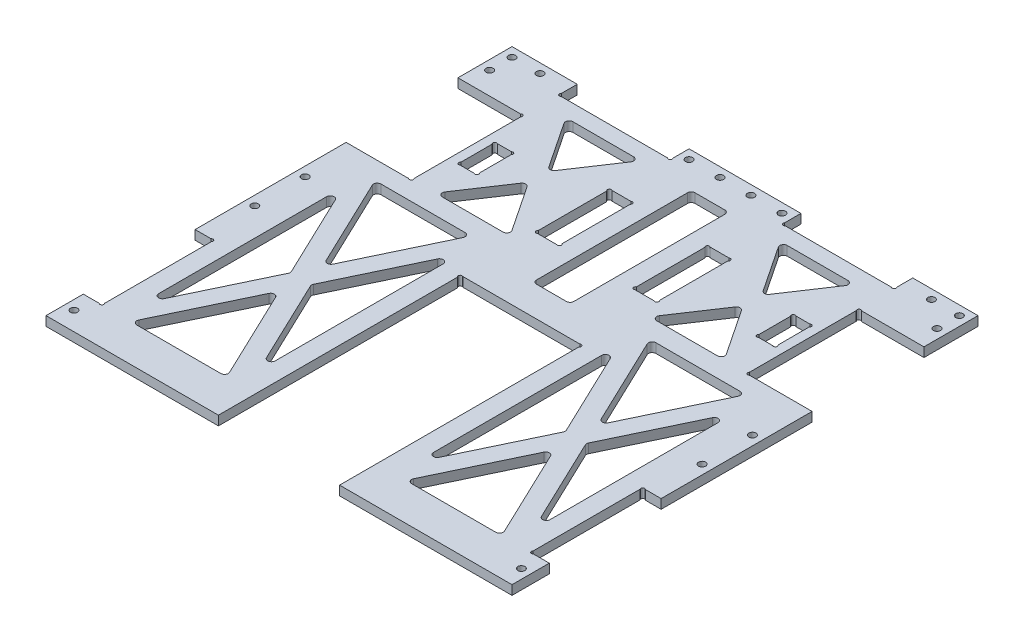
SolidWorks part; units mm, degrees
material "7050-T73510"
ref_plane "Front Plane" through (0, 0, 0) normal (0, 0, 1) x (1, 0, 0)
ref_plane "Top Plane" through (0, 0, 0) normal (0, 1, 0) x (1, 0, 0)
ref_plane "Right Plane" through (0, 0, 0) normal (1, 0, 0) x (0, 0, -1)
sketch "Sketch1" plane through (0, 0, 0) normal (0, 1, 0) x (1, 0, 0)
  line L0 (0, -55) -> (0, 55) construction
  line L1 (-158.75, -76.2) -> (158.75, -76.2)
  line L2 (-158.75, -76.2) -> (-158.75, 76.2)
  line L3 (-158.75, 76.2) -> (158.75, 76.2)
  line L4 (158.75, -76.2) -> (158.75, 76.2)
  line L5 (-158.75, -76.2) -> (158.75, 76.2) construction
  line L6 (-158.75, 76.2) -> (158.75, -76.2) construction
  line L7 (-158.75, -76.2) -> (-25.4, -76.2)
  line L8 (-158.75, -76.2) -> (-158.75, -241.3)
  line L9 (-158.75, -241.3) -> (-25.4, -241.3)
  line L10 (-25.4, -76.2) -> (-25.4, -241.3)
  line L11 (25.4, -76.2) -> (25.4, -241.3)
  line L12 (158.75, -241.3) -> (25.4, -241.3)
  line L13 (158.75, -76.2) -> (158.75, -241.3)
  line L14 (158.75, -76.2) -> (25.4, -76.2)
  line L15 (-41.275, -76.2) -> (-41.275, -241.3)
  line L16 (41.275, -76.2) -> (41.275, -241.3)
  point P0 (0, 0)
  dimension "D1" = 317.5
  dimension "D2" = 152.4
  dimension "D3" = 317.5
  dimension "D4" = 50.8
  dimension "D5" = 15.875
extrude "Boss-Extrude1" add sketch "Sketch1" along normal blind 6.35 contours L15 L1 L8 L9 | L14 L16 L12 L13 | L1 L7 L14 L4 L3 L2 region at (0, 0, 0) region at (-100.0125, 0, 158.75) region at (100.0125, 0, 158.75)
sketch "Sketch2" plane through (0, 6.35, 0) normal (0, 1, 0) x (1, 0, 0)
  line L0 (158.75, -241.3) -> (158.75, 76.2) construction
  line L1 (158.75, 39.37) -> (114.3, 39.37)
  line L2 (158.75, 39.37) -> (158.75, -36.83)
  line L3 (158.75, -36.83) -> (114.3, -36.83)
  line L4 (114.3, 39.37) -> (114.3, -36.83)
  line L5 (-158.75, 76.2) -> (158.75, 76.2) construction
  line L6 (158.75, -139.7) -> (146.05, -139.7)
  line L7 (158.75, -139.7) -> (158.75, -215.9)
  line L8 (158.75, -215.9) -> (146.05, -215.9)
  line L9 (146.05, -139.7) -> (146.05, -215.9)
  line L10 (0, -3.4925) -> (0, 3.4925) construction
  line L11 (-158.75, -215.9) -> (-146.05, -215.9)
  line L12 (-146.05, -139.7) -> (-146.05, -215.9)
  line L13 (-158.75, -139.7) -> (-146.05, -139.7)
  line L14 (-158.75, -139.7) -> (-158.75, -215.9)
  line L15 (-158.75, -36.83) -> (-114.3, -36.83)
  line L16 (-114.3, 39.37) -> (-114.3, -36.83)
  line L17 (-158.75, 39.37) -> (-114.3, 39.37)
  line L18 (-158.75, 39.37) -> (-158.75, -36.83)
  line L19 (-114.3, 63.5) -> (-38.1, 63.5)
  line L20 (114.3, 76.2) -> (38.1, 76.2)
  line L21 (114.3, 76.2) -> (114.3, 63.5)
  line L22 (114.3, 63.5) -> (38.1, 63.5)
  line L23 (38.1, 76.2) -> (38.1, 63.5)
  line L24 (-38.1, 76.2) -> (-38.1, 63.5)
  line L25 (-114.3, 76.2) -> (-38.1, 76.2)
  line L26 (-114.3, 76.2) -> (-114.3, 63.5)
  dimension "D1" = 44.45
  dimension "D2" = 12.7
  dimension "D3" = 76.2
  dimension "D4" = 76.2
  dimension "D5" = 36.83
  dimension "D6" = 215.9
  dimension "D7" = 76.2
  dimension "D8" = 12.7
  dimension "D9" = 76.2
extrude "Cut-Extrude1" cut sketch "Sketch2" against normal through all
sketch "Sketch4" plane through (0, 6.35, 0) normal (0, 1, 0) x (1, 0, 0)
  line L0 (41.275, -76.2) -> (41.275, -241.3) construction
  line L1 (53.975, -215.9) -> (133.35, -215.9)
  line L2 (53.975, -215.9) -> (53.975, -49.53)
  line L3 (53.975, -49.53) -> (133.35, -49.53)
  line L4 (133.35, -215.9) -> (133.35, -49.53)
  line L5 (146.05, -139.7) -> (146.05, -215.9) construction
  line L6 (158.75, -241.3) -> (41.275, -241.3) construction
  line L7 (53.975, -215.9) -> (133.35, -49.53) construction
  line L8 (53.975, -49.53) -> (133.35, -215.9) construction
  line L9 (133.35, -201.1532) -> (61.0107, -49.53)
  line L10 (126.3143, -215.9) -> (53.975, -64.2768)
  line L11 (53.975, -201.1532) -> (126.3143, -49.53)
  line L12 (61.0107, -215.9) -> (133.35, -64.2768)
  line L13 (114.3, -36.83) -> (158.75, -36.83) construction
  line L14 (0, -3.4925) -> (0, 3.4925) construction
  line L15 (-53.975, -201.1532) -> (-126.3143, -49.53)
  line L16 (-126.3143, -215.9) -> (-53.975, -64.2768)
  line L17 (-133.35, -201.1532) -> (-61.0107, -49.53)
  line L18 (-61.0107, -215.9) -> (-133.35, -64.2768)
  line L19 (-53.975, -49.53) -> (-133.35, -49.53)
  line L20 (-133.35, -215.9) -> (-133.35, -49.53)
  line L21 (-53.975, -215.9) -> (-133.35, -215.9)
  line L22 (-53.975, -215.9) -> (-53.975, -49.53)
  point P18 (116.9135, -166.7022)
  dimension "D1" = 12.7
  dimension "D2" = 12.7
  dimension "D3" = 25.4
  dimension "D4" = 12.7
  dimension "D5" = 12.7
extrude "Cut-Extrude3" cut sketch "Sketch4" against normal through all contours L12 L9 L4 | L12 L1 L10 | L2 L11 L10 | L9 L11 L3 | L21 L18 L16 | L20 L17 L18 | L17 L19 L15 | L15 L22 L16 region at (93.6625, 6.35, 193.0873) region at (64.8589, 6.35, 132.715) region at (122.4661, 6.35, 132.715) region at (93.6625, 6.35, 72.3427) region at (-64.8589, 6.35, 132.715) region at (-93.6625, 6.35, 72.3427) region at (-93.6625, 6.35, 193.0873) region at (-122.4661, 6.35, 132.715)
sketch "Sketch3" plane through (0, 6.35, 0) normal (0, 1, 0) x (1, 0, 0)
  line L0 (-41.275, -76.2) -> (41.275, -76.2) construction
  line L1 (-41.275, -25.4) -> (-25.4, -25.4)
  line L2 (-41.275, -25.4) -> (-41.275, 25.4)
  line L3 (-41.275, 25.4) -> (-25.4, 25.4)
  line L4 (-25.4, -25.4) -> (-25.4, 25.4)
  line L5 (0, -3.4925) -> (0, 3.4925) construction
  line L6 (41.275, 25.4) -> (25.4, 25.4)
  line L7 (25.4, -25.4) -> (25.4, 25.4)
  line L8 (41.275, -25.4) -> (25.4, -25.4)
  line L9 (41.275, -25.4) -> (41.275, 25.4)
  line L10 (114.3, 39.37) -> (114.3, -36.83) construction
  line L11 (95.25, 13.97) -> (107.95, 13.97)
  line L12 (95.25, 13.97) -> (95.25, -11.43)
  line L13 (95.25, -11.43) -> (107.95, -11.43)
  line L14 (107.95, 13.97) -> (107.95, -11.43)
  line L15 (38.1, 63.5) -> (114.3, 63.5) construction
  line L16 (-95.25, -11.43) -> (-107.95, -11.43)
  line L17 (-107.95, 13.97) -> (-107.95, -11.43)
  line L18 (-95.25, 13.97) -> (-107.95, 13.97)
  line L19 (-95.25, 13.97) -> (-95.25, -11.43)
  dimension "D1" = 50.8
  dimension "D2" = 15.875
  dimension "D3" = 50.8
  dimension "D4" = 50.8
  dimension "D5" = 25.4
  dimension "D6" = 12.7
  dimension "D7" = 6.35
  dimension "D8" = 49.53
extrude "Cut-Extrude2" cut sketch "Sketch3" against normal through all
sketch "Sketch6" plane through (0, 6.35, 0) normal (0, 1, 0) x (1, 0, 0)
  line L0 (-25.4, -25.4) -> (-25.4, 25.4) construction
  line L1 (-19.05, 63.5) -> (19.05, 63.5)
  line L2 (-19.05, 63.5) -> (-19.05, -63.5)
  line L3 (-19.05, -63.5) -> (19.05, -63.5)
  line L4 (19.05, 63.5) -> (19.05, -63.5)
  line L5 (25.4, 25.4) -> (25.4, -25.4) construction
  line L6 (-38.1, 76.2) -> (38.1, 76.2) construction
  line L7 (-41.275, -76.2) -> (41.275, -76.2) construction
  line L8 (-19.05, -63.5) -> (19.05, 63.5) construction
  line L9 (19.05, -63.5) -> (-19.05, 63.5) construction
  line L10 (12.4204, -63.5) -> (-19.05, 41.4014)
  line L11 (-12.4204, 63.5) -> (19.05, -41.4014)
  line L12 (-19.05, -41.4014) -> (12.4204, 63.5)
  line L13 (19.05, 41.4014) -> (-12.4204, -63.5)
  dimension "D1" = 6.35
  dimension "D2" = 6.35
  dimension "D3" = 12.7
  dimension "D4" = 12.7
  dimension "D5" = 12.7
  dimension "D6" = 12.7
extrude "Cut-Extrude5" [suppressed] cut sketch "Sketch6" against normal through all contours L10 L13 L3 | L4 L13 L11 | L2 L12 L10 | L11 L12 L1
sketch "Sketch7" plane through (0, 6.35, 0) normal (0, 1, 0) x (1, 0, 0)
  line L0 (158.75, -139.7) -> (146.05, -139.7) construction
  line L1 (158.75, -139.7) -> (158.75, -36.83) construction
  line L2 (0, -3.4925) -> (0, 3.4925) construction
  line L3 (158.75, -241.3) -> (41.275, -241.3) construction
  line L4 (-38.1, 76.2) -> (-38.1, 63.5) construction
  line L5 (114.3, 76.2) -> (158.75, 76.2) construction
  line L6 (-38.1, 76.2) -> (38.1, 76.2) construction
  circle A0 centre (152.4, -105.41) radius 2.413
  circle A1 centre (152.4, -71.12) radius 2.413
  circle A8 centre (152.4, -228.6) radius 2.413
  circle A9 centre (152.4, 69.85) radius 2.413
  circle A10 centre (133.35, 69.85) radius 2.413
  circle A12 centre (152.4, 54.61) radius 2.413
  circle A19 centre (-152.4, -228.6) radius 2.413
  circle A20 centre (-31.75, 69.85) radius 2.413
  circle A21 centre (-10.668, 69.85) radius 2.413
  circle A22 centre (10.414, 69.85) radius 2.413
  circle A23 centre (31.496, 69.85) radius 2.413
  circle A24 centre (-152.4, 54.61) radius 2.413
  circle A25 centre (-133.35, 69.85) radius 2.413
  circle A26 centre (-152.4, 69.85) radius 2.413
  circle A27 centre (-152.4, -71.12) radius 2.413
  circle A28 centre (-152.4, -105.41) radius 2.413
  dimension "D1" = 4.826
  dimension "D3" = 6.35
  dimension "D5" = 12.7
  dimension "D6" = 6.35
  dimension "D9" = 4.826
  dimension "D2" = 34.29
  dimension "D8" = 2
  dimension "D10" = 6.35
  dimension "D11" = 6.35
  dimension "D4" = 2
  dimension "D7" = 2
  dimension "D12" = 4
extrude "Cut-Extrude6" cut sketch "Sketch7" against normal through all
sketch "Sketch5" plane through (0, 6.35, 0) normal (0, 1, 0) x (1, 0, 0)
  line L0 (0, -3.4925) -> (0, 3.4925) construction
  line L2 (-38.1, 76.2) -> (38.1, 76.2) construction
  line L3 (41.275, -25.4) -> (41.275, 25.4) construction
  line L4 (114.3, 63.5) -> (38.1, 63.5) construction
  circle A0 centre (12.7, 63.5) radius 6.35
  circle A1 centre (12.7, 50.8) radius 6.35
  circle A2 centre (12.7, 38.1) radius 6.35
  circle A3 centre (12.7, 25.4) radius 6.35
  circle A4 centre (12.7, 12.7) radius 6.35
  circle A11 centre (0, 50.8) radius 6.35
  circle A12 centre (0, 38.1) radius 6.35
  circle A13 centre (0, 25.4) radius 6.35
  circle A14 centre (0, 12.7) radius 6.35
  circle A21 centre (-12.7, 50.8) radius 6.35
  circle A22 centre (-12.7, 38.1) radius 6.35
  circle A23 centre (-12.7, 25.4) radius 6.35
  circle A24 centre (-12.7, 12.7) radius 6.35
  circle A31 centre (0, 63.5) radius 6.35
  circle A32 centre (-12.7, 63.5) radius 6.35
  circle A33 centre (53.975, 50.8) radius 3.175
  circle A34 centre (66.675, 50.8) radius 3.175
  circle A35 centre (79.375, 50.8) radius 3.175
  circle A36 centre (66.675, 38.1) radius 3.175
  circle A37 centre (79.375, 38.1) radius 3.175
  circle A38 centre (66.675, 25.4) radius 3.175
  circle A39 centre (79.375, 25.4) radius 3.175
  circle A40 centre (66.675, 12.7) radius 3.175
  circle A41 centre (79.375, 12.7) radius 3.175
  circle A42 centre (66.675, 0) radius 3.175
  circle A43 centre (79.375, 0) radius 3.175
  circle A44 centre (66.675, -12.7) radius 3.175
  circle A45 centre (79.375, -12.7) radius 3.175
  circle A46 centre (66.675, -25.4) radius 3.175
  circle A47 centre (79.375, -25.4) radius 3.175
  circle A48 centre (66.675, -38.1) radius 3.175
  circle A49 centre (79.375, -38.1) radius 3.175
  circle A50 centre (53.975, 38.1) radius 3.175
  circle A51 centre (53.975, 25.4) radius 3.175
  circle A52 centre (53.975, 12.7) radius 3.175
  circle A53 centre (53.975, 0) radius 3.175
  circle A54 centre (53.975, -12.7) radius 3.175
  circle A55 centre (53.975, -25.4) radius 3.175
  circle A56 centre (53.975, -38.1) radius 3.175
  circle A57 centre (-53.975, -38.1) radius 3.175
  circle A58 centre (-53.975, -25.4) radius 3.175
  circle A59 centre (-53.975, -12.7) radius 3.175
  circle A60 centre (-53.975, 0) radius 3.175
  circle A61 centre (-53.975, 12.7) radius 3.175
  circle A62 centre (-53.975, 25.4) radius 3.175
  circle A63 centre (-53.975, 38.1) radius 3.175
  circle A64 centre (-79.375, -38.1) radius 3.175
  circle A65 centre (-66.675, -38.1) radius 3.175
  circle A66 centre (-79.375, -25.4) radius 3.175
  circle A67 centre (-66.675, -25.4) radius 3.175
  circle A68 centre (-79.375, -12.7) radius 3.175
  circle A69 centre (-66.675, -12.7) radius 3.175
  circle A70 centre (-79.375, 0) radius 3.175
  circle A71 centre (-66.675, 0) radius 3.175
  circle A72 centre (-79.375, 12.7) radius 3.175
  circle A73 centre (-66.675, 12.7) radius 3.175
  circle A74 centre (-79.375, 25.4) radius 3.175
  circle A75 centre (-66.675, 25.4) radius 3.175
  circle A76 centre (-79.375, 38.1) radius 3.175
  circle A77 centre (-66.675, 38.1) radius 3.175
  circle A78 centre (-79.375, 50.8) radius 3.175
  circle A79 centre (-66.675, 50.8) radius 3.175
  circle A80 centre (-53.975, 50.8) radius 3.175
  dimension "D1" = 12.7
  dimension "D6" = 6.35
  dimension "D2" = 12.7
  dimension "D3" = 12.7
  dimension "D7" = 12.7
  dimension "D8" = 12.7
  dimension "D4" = 5
  dimension "D5" = 3
  dimension "D9" = 3
  dimension "D10" = 8
sketch "Sketch10" plane through (0, 6.35, 0) normal (0, 1, 0) x (1, 0, 0)
  line L0 (0, -3.4925) -> (0, 3.4925) construction
  circle A0 centre (-146.9728, -215.0274) radius 1.27
  circle A1 centre (-147.0286, -140.5095) radius 1.27
  circle A2 centre (-115.2095, -35.9436) radius 1.27
  circle A3 centre (-115.2533, 38.5309) radius 1.27
  circle A4 centre (-113.4221, 64.4177) radius 1.27
  circle A5 centre (-39.0797, 64.3081) radius 1.27
  circle A8 centre (-107.1935, 12.9499) radius 1.27
  circle A9 centre (-96.0928, 13.02) radius 1.27
  circle A10 centre (-107.2327, -10.382) radius 1.27
  circle A11 centre (-96.0288, -10.4268) radius 1.27
  circle A12 centre (-40.5811, 24.3363) radius 1.27
  circle A13 centre (-26.2184, 24.4288) radius 1.27
  circle A15 centre (-40.5236, -24.3761) radius 1.27
  circle A16 centre (-25.9957, -24.2784) radius 1.27
  circle A17 centre (-40.5722, -77.2578) radius 1.27
  circle A18 centre (40.5722, -77.2578) radius 1.27
  circle A19 centre (25.9957, -24.2784) radius 1.27
  circle A20 centre (40.5236, -24.3761) radius 1.27
  circle A21 centre (26.2184, 24.4288) radius 1.27
  circle A22 centre (40.5811, 24.3363) radius 1.27
  circle A23 centre (96.0288, -10.4268) radius 1.27
  circle A24 centre (107.2327, -10.382) radius 1.27
  circle A25 centre (96.0928, 13.02) radius 1.27
  circle A26 centre (107.1935, 12.9499) radius 1.27
  circle A27 centre (39.0797, 64.3081) radius 1.27
  circle A28 centre (113.4221, 64.4177) radius 1.27
  circle A29 centre (115.2533, 38.5309) radius 1.27
  circle A30 centre (115.2095, -35.9436) radius 1.27
  circle A31 centre (147.0286, -140.5095) radius 1.27
  circle A32 centre (146.9728, -215.0274) radius 1.27
extrude "Cut-Extrude7" cut sketch "Sketch10" against normal through all
sketch "Sketch12" plane through (0, 6.35, 0) normal (0, 1, 0) x (1, 0, 0)
  line L0 (-98.425, 52.6142) -> (-47.625, 52.6142)
  line L1 (-47.625, 52.6142) -> (-73.025, 14.5142)
  line L2 (-73.025, 14.5142) -> (-98.425, 52.6142)
  line L3 (-94.4842, 8.1642) -> (-61.9728, 8.1642) construction
  line L4 (-114.3, 39.37) -> (-114.3, -36.83) construction
  line L5 (-47.625, -36.2858) -> (-73.025, 1.8142)
  line L6 (-98.425, -36.2858) -> (-47.625, -36.2858)
  line L7 (-73.025, 1.8142) -> (-98.425, -36.2858)
  line L8 (0, -3.4925) -> (0, 3.4925) construction
  line L9 (94.4842, 8.1642) -> (61.9728, 8.1642) construction
  line L10 (73.025, 1.8142) -> (98.425, -36.2858)
  line L11 (98.425, -36.2858) -> (47.625, -36.2858)
  line L12 (47.625, -36.2858) -> (73.025, 1.8142)
  line L13 (73.025, 14.5142) -> (98.425, 52.6142)
  line L14 (47.625, 52.6142) -> (73.025, 14.5142)
  line L15 (98.425, 52.6142) -> (47.625, 52.6142)
  line L23 (-12.7, -55.6542) -> (12.7, -55.6542)
  line L24 (-12.7, -55.6542) -> (-12.7, 52.2958)
  line L25 (-12.7, 52.2958) -> (12.7, 52.2958)
  line L26 (12.7, -55.6542) -> (12.7, 52.2958)
  point P6 (-73.025, 52.6142)
  point P25 (0, -55.6542)
  dimension "D1" = 6.35
  dimension "D2" = 44.45
  dimension "D3" = 50.8
  dimension "D4" = 41.275
  dimension "D5" = 25.4
  dimension "D6" = 107.95
extrude "Cut-Extrude9" cut sketch "Sketch12" against normal through all
fillet "Fillet1" radius 2.54 20 edges at (-12.7, 3.175, 55.6542) (-12.7, 3.175, -52.2958) (-133.35, 3.175, 64.2768) (-133.35, 3.175, 201.1532) (-126.3143, 3.175, 215.9) (-61.0107, 3.175, 215.9) (-93.6625, 3.175, 147.4618) (-86.6268, 3.175, 132.715) (-53.975, 3.175, 64.2768) (-53.975, 3.175, 201.1532) (-93.6625, 3.175, 117.9682) (-100.6982, 3.175, 132.715) (-61.0107, 3.175, 49.53) (-126.3143, 3.175, 49.53) (-98.425, 3.175, 36.2858) (-47.625, 3.175, 36.2858) (-73.025, 3.175, -1.8142) (-73.025, 3.175, -14.5142) (-47.625, 3.175, -52.6142) (-98.425, 3.175, -52.6142)
fillet "Fillet2" radius 2.54 20 edges at (53.975, 3.175, 64.2768) (133.35, 3.175, 64.2768) (93.6625, 3.175, 147.4618) (100.6982, 3.175, 132.715) (53.975, 3.175, 201.1532) (61.0107, 3.175, 215.9) (133.35, 3.175, 201.1532) (86.6268, 3.175, 132.715) (126.3143, 3.175, 215.9) (93.6625, 3.175, 117.9682) (61.0107, 3.175, 49.53) (126.3143, 3.175, 49.53) (73.025, 3.175, -1.8142) (47.625, 3.175, 36.2858) (98.425, 3.175, 36.2858) (98.425, 3.175, -52.6142) (73.025, 3.175, -14.5142) (12.7, 3.175, 55.6542) (12.7, 3.175, -52.2958) (47.625, 3.175, -52.6142)
